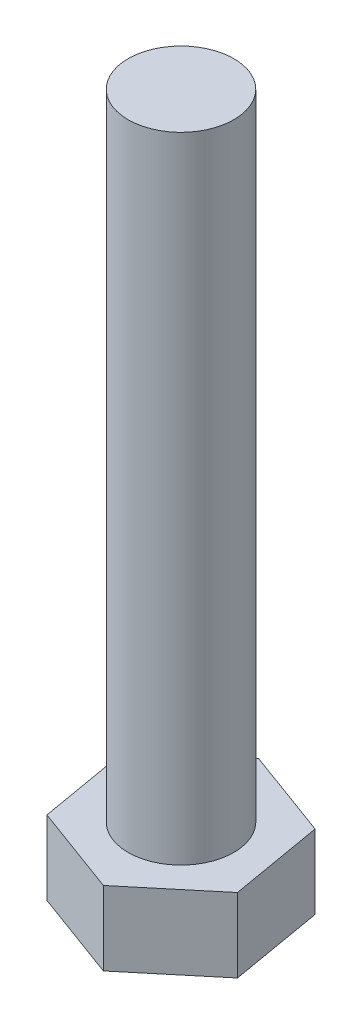
SolidWorks part; units mm, degrees
ref_plane "Спереди" through (0, 0, 0) normal (0, 0, 1) x (1, 0, 0)
ref_plane "Сверху" through (0, 0, 0) normal (0, 1, 0) x (1, 0, 0)
ref_plane "Справа" through (0, 0, 0) normal (1, 0, 0) x (0, 0, -1)
sketch "Эскиз1" plane through (0, 0, 0) normal (0, 1, 0) x (1, 0, 0)
  line L1 (4.2233, -1.5536) -> (3.4571, 2.8807)
  line L2 (3.4571, 2.8807) -> (-0.7661, 4.4343)
  line L3 (-0.7661, 4.4343) -> (-4.2233, 1.5536)
  line L4 (-4.2233, 1.5536) -> (-3.4571, -2.8807)
  line L5 (-3.4571, -2.8807) -> (0.7661, -4.4343)
  line L6 (0.7661, -4.4343) -> (4.2233, -1.5536)
  circle A0 centre (0, 0) radius 4.5 construction
  circle A1 centre (0, 0) radius 3.8971 construction
  dimension "D1" = 9
extrude "Вытянуть1" add sketch "Эскиз1" along normal blind 3.5
sketch "Эскиз2" plane through (0, 3.5, 0) normal (0, 1, 0) x (1, 0, 0)
  circle A0 centre (0, 0) radius 2.5
  dimension "D1" = 5
extrude "Вытянуть2" add sketch "Эскиз2" along normal blind 30
